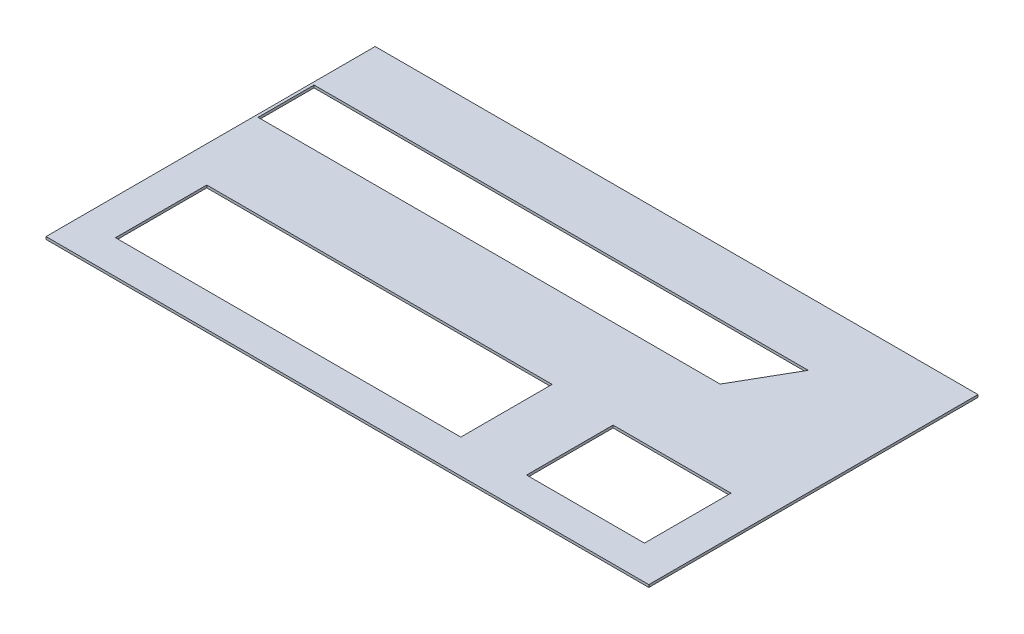
SolidWorks part; units mm, degrees
material "Particle Board"
ref_plane "Front Plane" through (0, 0, 0) normal (0, 0, 1) x (1, 0, 0)
ref_plane "Top Plane" through (0, 0, 0) normal (0, 1, 0) x (1, 0, 0)
ref_plane "Right Plane" through (0, 0, 0) normal (1, 0, 0) x (0, 0, -1)
sketch "Sketch1" plane through (0, 0, 0) normal (0, 1, 0) x (1, 0, 0)
  line L1 (0, 0) -> (1518.68, 0)
  line L2 (0, 0) -> (0, 829.31)
  line L3 (0, 829.31) -> (1518.68, 829.31)
  line L4 (1518.68, 0) -> (1518.68, 829.31)
  dimension "D1" = 1518.68
  dimension "D2" = 829.31
extrude "Boss-Extrude1" add sketch "Sketch1" along normal blind 6.35
sketch "Sketch2" plane through (0, 6.35, 0) normal (0, 1, 0) x (1, 0, 0)
  line L0 (0, 829.31) -> (0, 0) construction
  line L1 (90, 85) -> (960, 85)
  line L2 (90, 85) -> (90, 315)
  line L3 (90, 315) -> (960, 315)
  line L4 (960, 85) -> (960, 315)
  line L5 (0, 0) -> (1518.68, 0) construction
  line L6 (1518.68, 0) -> (1518.68, 829.31) construction
  line L7 (7, 668.31) -> (1252, 668.31)
  line L8 (7, 668.31) -> (7, 527.31)
  line L9 (7, 527.31) -> (1171, 527.31)
  line L11 (1422.68, 303) -> (1125.68, 303)
  line L12 (1422.68, 303) -> (1422.68, 85)
  line L13 (1422.68, 85) -> (1125.68, 85)
  line L14 (1125.68, 303) -> (1125.68, 85)
  line L15 (1252, 668.31) -> (1171, 527.31)
  line L16 (1518.68, 829.31) -> (0, 829.31) construction
  dimension "D1" = 870
  dimension "D2" = 230
  dimension "D3" = 90
  dimension "D4" = 85
  dimension "D5" = 85
  dimension "D6" = 218
  dimension "D7" = 96
  dimension "D8" = 297
  dimension "D9" = 7
  dimension "D10" = 1245
  dimension "D11" = 1164
  dimension "D12" = 161
  dimension "D13" = 141
extrude "Cut-Extrude1" cut sketch "Sketch2" against normal up to next
